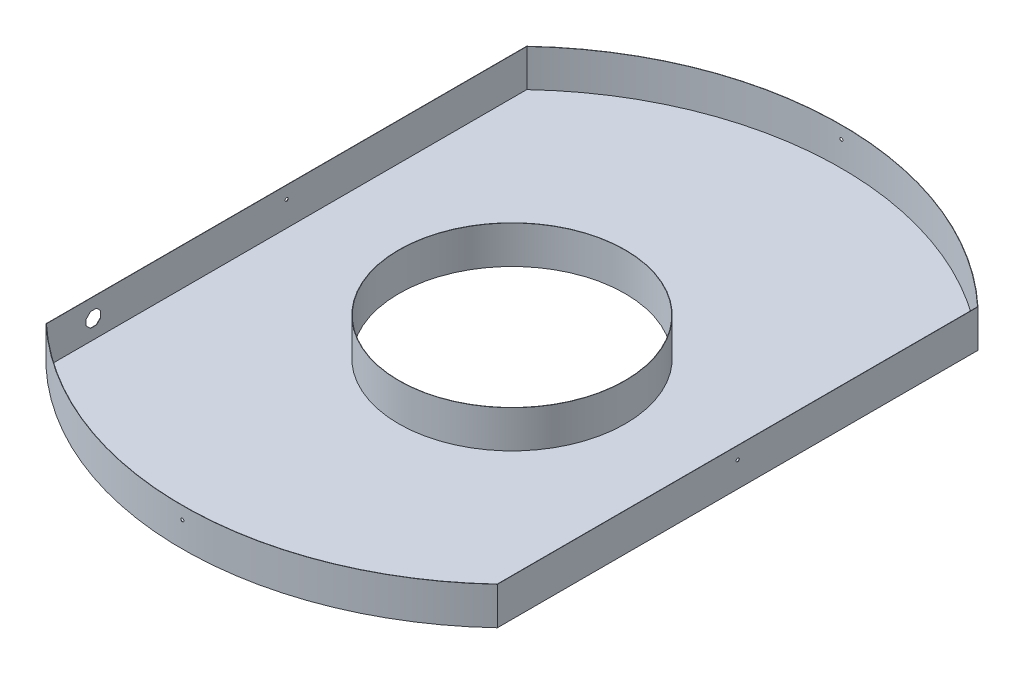
SolidWorks part; units mm, degrees
material "1345 Alloy"
ref_plane "Front Plane" through (0, 0, 0) normal (0, 0, 1) x (1, 0, 0)
ref_plane "Top Plane" through (0, 0, 0) normal (0, 1, 0) x (1, 0, 0)
ref_plane "Right Plane" through (0, 0, 0) normal (1, 0, 0) x (0, 0, -1)
sketch "Sketch1" plane through (0, 0, 0) normal (0, 1, 0) x (1, 0, 0)
  circle A0 centre (0, 0) radius 1750
extrude "Boss-Extrude1" add sketch "Sketch1" along normal blind 500
sketch "Sketch2" plane through (0, 500, 0) normal (0, 1, 0) x (1, 0, 0)
  circle A0 centre (0, 0) radius 900
extrude "Cut-Extrude2" cut sketch "Sketch2" against normal blind 300
sketch "Sketch10" plane through (0, 500, 0) normal (0, 1, 0) x (1, 0, 0)
  line L1 (-2200.588, -2811.5432) -> (2200.588, -2811.5432)
  line L2 (-2200.588, -2811.5432) -> (-2200.588, 2811.5432)
  line L3 (-2200.588, 2811.5432) -> (2200.588, 2811.5432)
  line L4 (2200.588, -2811.5432) -> (2200.588, 2811.5432)
  line L5 (-2200.588, -2811.5432) -> (2200.588, 2811.5432) construction
  line L6 (-2200.588, 2811.5432) -> (2200.588, -2811.5432) construction
  line L7 (-1198.0599, -2169.9586) -> (1198.0599, -2169.9586)
  line L8 (-1198.0599, -2169.9586) -> (-1198.0599, 2169.9586)
  line L9 (-1198.0599, 2169.9586) -> (1198.0599, 2169.9586)
  line L10 (1198.0599, -2169.9586) -> (1198.0599, 2169.9586)
  line L11 (-1198.0599, -2169.9586) -> (1198.0599, 2169.9586) construction
  line L12 (-1198.0599, 2169.9586) -> (1198.0599, -2169.9586) construction
  point P0 (0, 0)
  point P6 (0, 0)
extrude "Cut-Extrude10" cut sketch "Sketch10" against normal through all both and the other way through all
sketch "Sketch3" plane through (0, 0, 0) normal (0, -1, 0) x (1, 0, 0)
  circle A0 centre (0, 0) radius 600
extrude "Cut-Extrude3" cut sketch "Sketch3" against normal blind 300
shell "Shell1" thickness 1.5 removed face at (0, 500, 900)
sketch "Sketch11" plane through (0, 200, 0) normal (0, 1, 0) x (1, 0, 0)
  line L1 (-1546.6788, 2430.4952) -> (1546.6788, 2430.4952)
  line L2 (-1546.6788, 2430.4952) -> (-1546.6788, -2430.4952)
  line L3 (-1546.6788, -2430.4952) -> (1546.6788, -2430.4952)
  line L4 (1546.6788, 2430.4952) -> (1546.6788, -2430.4952)
  line L5 (-1546.6788, 2430.4952) -> (1546.6788, -2430.4952) construction
  line L6 (-1546.6788, -2430.4952) -> (1546.6788, 2430.4952) construction
  point P0 (0, 0)
extrude "Cut-Extrude11" cut sketch "Sketch11" along normal through all
ref_plane "Plane1" through (0, 0, 2000) normal (0, 0, 1) x (1, 0, 0)
sketch "Sketch7" plane through (0, 0, 2000) normal (0, 0, 1) x (1, 0, 0)
  circle A0 centre (0, 133.8976) radius 8.382
extrude "Cut-Extrude6" cut sketch "Sketch7" against normal blind 900
pattern_circular "CirPattern1" count 4 over 360 about axis through (0, 500, 0) along (0, -1, 0) of "Cut-Extrude6" reverse direction yes
ref_plane "Plane2" through (-1237.4369, 0, 1237.4369) normal (-0.7071, 0, 0.7071) x (0, -1, 0)
sketch "Sketch12" plane through (-1198.0599, 0, 0) normal (-1, 0, 0) x (0, 0, 1)
  line L0 (986.4823, 84.2757) -> (1009.035, 61.7229)
  line L1 (1009.035, 61.7229) -> (1040.9295, 61.7229)
  line L2 (1040.9295, 61.7229) -> (1063.4823, 84.2757)
  line L3 (1063.4823, 84.2757) -> (1063.4823, 116.1701)
  line L4 (1063.4823, 116.1701) -> (1040.9295, 138.7229)
  line L5 (1040.9295, 138.7229) -> (1009.035, 138.7229)
  line L6 (1009.035, 138.7229) -> (986.4823, 116.1701)
  line L7 (986.4823, 116.1701) -> (986.4823, 84.2757)
  circle A0 centre (1024.9823, 100.2229) radius 38.5 construction
extrude "Cut-Extrude13" cut sketch "Sketch12" against normal blind 10
sketch "Sketch13" plane through (0, 200, 0) normal (0, 1, 0) x (1, 0, 0)
  circle A0 centre (0, 0) radius 901.5 construction
  circle A1 centre (0, 0) radius 901.5
  circle A2 centre (0, 0) radius 601.5
extrude "Cut-Extrude14" cut sketch "Sketch13" against normal blind 10
